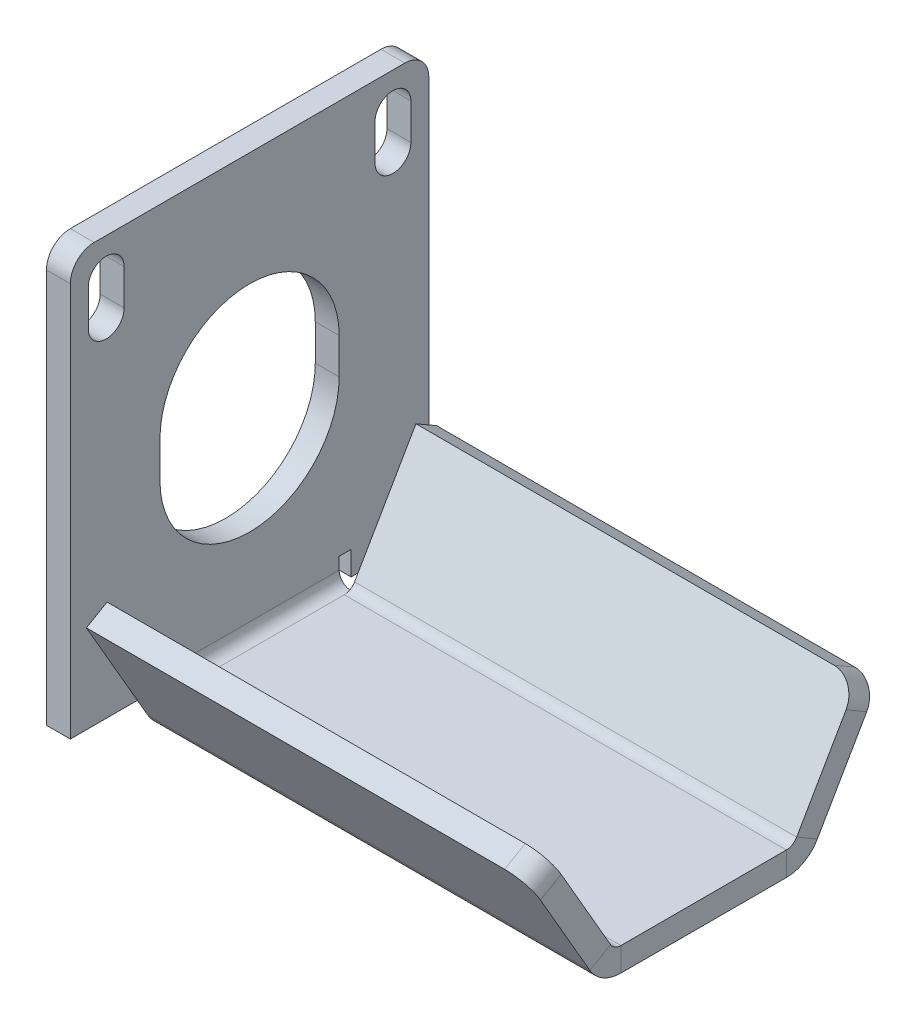
SolidWorks part; units mm, degrees
note: The reader was unsure of these and kept them because the rebuilt part matched: flange length of "Edge-Flange1", "Edge-Flange3".
ref_plane "Front Plane" through (0, 0, 0) normal (0, 0, 1) x (1, 0, 0)
ref_plane "Top Plane" through (0, 0, 0) normal (0, 1, 0) x (1, 0, 0)
ref_plane "Right Plane" through (0, 0, 0) normal (1, 0, 0) x (0, 0, -1)
sketch "Sketch1" plane through (23.5904, 0, 0) normal (1, 0, 0) x (0, 0, -1)
  line L1 (15.3078, 1219.7013) -> (-14.6922, 1219.7013)
  line L2 (15.3078, 1219.7013) -> (15.3078, 1184.7013)
  line L3 (15.3078, 1184.7013) -> (-14.6922, 1184.7013)
  line L4 (-14.6922, 1219.7013) -> (-14.6922, 1184.7013)
  circle A0 centre (0.3078, 1199.7013) radius 10 construction
  dimension "D2" = 20
  dimension "D1" = 30
  dimension "D3" = 35
sheet metal parameters "Sheet-Metal1" thickness 2 parameters "D1"=1
base flange "Base-Flange1" sketch "Sketch1" thickness 2 reverse thickness direction yes parameters "D1"=1
edge flange "Edge-Flange1" sketch "Sketch6" flange angle 90 flange length 40 flange position material outside bend radius 1 thickness 2 relief rectangular parameters "D6"=10
sketch "Sketch6" plane through (25.5904, 1184.7013, 0) normal (0, -1, 0) x (0, 0, -1)
  line L0 (-14.6922, 0) -> (15.3078, 0) construction
  line L1 (-7.1922, 0) -> (7.8078, 0)
  line L2 (-7.1922, 0) -> (-7.1922, 38)
  line L3 (-7.1922, 38) -> (7.8078, 38)
  line L4 (7.8078, 38) -> (7.8078, 0)
  dimension "D1" = 38
  dimension "D2" = 7.5
  dimension "D3" = 7.5
bend "EdgeBend1" bend radius 1 bend angle 90 parameters "D5"=1
sketch "Sketch7" plane through (25.5904, 0, 0) normal (1, 0, 0) x (0, 0, -1)
  line L0 (15.3078, 1219.7013) -> (-14.6922, 1219.7013) construction
  line L1 (15.3078, 1184.7013) -> (15.3078, 1219.7013) construction
  line L2 (-14.6922, 1219.7013) -> (-14.6922, 1184.7013) construction
  line L3 (-10.1922, 1216.7013) -> (-10.1922, 1213.7013)
  line L4 (-13.1922, 1216.7013) -> (-13.1922, 1213.7013)
  line L5 (10.8078, 1216.7013) -> (10.8078, 1213.7013)
  line L6 (13.8078, 1216.7013) -> (13.8078, 1213.7013)
  arc A0 (13.8078, 1216.7013) -> (10.8078, 1216.7013) centre (12.3078, 1216.7013) ccw
  arc A1 (-10.1922, 1216.7013) -> (-13.1922, 1216.7013) centre (-11.6922, 1216.7013) ccw
  arc A2 (-13.1922, 1213.7013) -> (-10.1922, 1213.7013) centre (-11.6922, 1213.7013) ccw
  arc A3 (10.8078, 1213.7013) -> (13.8078, 1213.7013) centre (12.3078, 1213.7013) ccw
  dimension "D1" = 3
  dimension "D2" = 3
  dimension "D11" = 3
  dimension "D12" = 3
  dimension "D3" = 3
  dimension "D4" = 3
  dimension "D5" = 3
  dimension "D6" = 3
  dimension "D7" = 3
  dimension "D8" = 3
  dimension "D9" = 3
  dimension "D10" = 3
extrude "Cut-Extrude1" cut sketch "Sketch7" against normal up to next normal cut yes
sketch "Sketch8" plane through (25.5904, 0, 0) normal (1, 0, 0) x (0, 0, -1)
  line L0 (0.3078, 1199.7013) -> (0.3078, 1202.7013) construction
  line L1 (0.3078, -0.2987) -> (0.3078, 1224.7013) construction
  line L2 (-7.1922, 1199.7013) -> (-7.1922, 1202.7013)
  line L3 (7.8078, 1199.7013) -> (7.8078, 1202.7013)
  arc A0 (-7.1922, 1199.7013) -> (7.8078, 1199.7013) centre (0.3078, 1199.7013) ccw
  arc A1 (7.8078, 1202.7013) -> (-7.1922, 1202.7013) centre (0.3078, 1202.7013) ccw
  point P5 (0.3078, 1201.2013)
  dimension "D1" = 15
  dimension "D2" = 3
extrude "Cut-Extrude2" cut sketch "Sketch8" against normal up to next normal cut yes
edge flange "Edge-Flange3" sketch "Sketch27" flange profiles "Sketch27", "Sketch28" flange angle 120 flange length 12 flange position material outside bend radius 1 thickness 2 relief none parameters "D6"=10, "D8"=1
sketch "Sketch27" plane through (0, 1184.7013, 7.1922) normal (0, -0.5, 0.866) x (1, 0, 0)
  line L0 (63.5904, 0) -> (26.5904, 0) construction
  line L1 (63.5904, 0) -> (26.5904, 0)
  line L2 (26.5904, 0) -> (26.5904, 10.8453)
  line L3 (26.5904, 10.8453) -> (63.5904, 10.8453)
  line L4 (63.5904, 10.8453) -> (63.5904, 0)
sketch "Sketch28" plane through (0, 1184.7013, -7.8078) normal (0, -0.5, -0.866) x (-1, 0, 0)
  line L0 (-26.5904, 0) -> (-63.5904, 0) construction
  line L1 (-26.5904, 0) -> (-63.5904, 0)
  line L2 (-63.5904, 0) -> (-63.5904, 10.8453)
  line L3 (-63.5904, 10.8453) -> (-26.5904, 10.8453)
  line L4 (-26.5904, 10.8453) -> (-26.5904, 0)
bend "EdgeBend4" bend radius 1 bend angle 60 parameters "D5"=1
bend "EdgeBend5" bend radius 1 bend angle 60 parameters "D5"=3
fillet "Fillet5" radius 2 4 edges at (24.5904, 1219.7013, 14.6922) (24.5904, 1219.7013, -15.3078) (63.5904, 1193.5936, 13.4808) (63.5904, 1193.5936, -14.0965)
flat pattern "Flat-Pattern1" [suppressed]
sketch "Bend-Lines1" plane through (25.5904, 0, 0) normal (1, 0, 0) x (0, 0, -1)
  line L0 (-7.1922, 1184.1305) -> (7.8078, 1184.1305) construction
  line L1 (-7.1922, 1184.1305) -> (7.8078, 1184.1305) construction
  line L2 (8.2777, 1182.5597) -> (8.2777, 1145.5597) construction
  line L3 (-7.662, 1145.5597) -> (-7.662, 1182.5597) construction
  line L4 (8.2777, 1182.5597) -> (8.2777, 1145.5597) construction
  line L5 (-7.662, 1145.5597) -> (-7.662, 1182.5597) construction
  point P2 (-7.5634, 1145.5597)
  point P3 (-7.5634, 1180.5597)
  point P4 (8.179, 1180.5597)
  point P5 (8.179, 1145.5597)
sketch3d "Bounding-Box1" [suppressed]
  line L0 (-34.285, 35, 0) -> (-34.285, -39.1416, 0) construction
  line L1 (4.285, 35, 0) -> (4.285, -39.1416, 0) construction
  line L2 (-34.285, 35, 0) -> (4.285, 35, 0) construction
  line L3 (-34.285, -39.1416, 0) -> (4.285, -39.1416, 0) construction
bend of the flat pattern "Flatten-<EdgeBend1>1"
bend of the flat pattern "Flatten-<EdgeBend4>1"
bend of the flat pattern "Flatten-<EdgeBend5>1"
fillet "Fillet2" [suppressed] radius 1
sketch "Sketch29" [suppressed] plane through (25.5904, 0, 0) normal (1, 0, 0) x (0, 0, -1)
  line L1 (-8.1922, 1184.7013) -> (-9.1922, 1184.7013)
  line L2 (-8.1922, 1184.7013) -> (-8.1922, 1186.7013)
  line L3 (-8.1922, 1186.7013) -> (-9.1922, 1186.7013)
  line L4 (-9.1922, 1184.7013) -> (-9.1922, 1186.7013)
  line L5 (8.8078, 1184.7013) -> (9.8078, 1184.7013)
  line L6 (8.8078, 1184.7013) -> (8.8078, 1186.7013)
  line L7 (8.8078, 1186.7013) -> (9.8078, 1186.7013)
  line L8 (9.8078, 1184.7013) -> (9.8078, 1186.7013)
  dimension "D1" = 1
  dimension "D2" = 1
extrude "Cut-Extrude7" [suppressed] cut sketch "Sketch29" against normal up to next
fillet "Fillet3" [suppressed] radius 1
